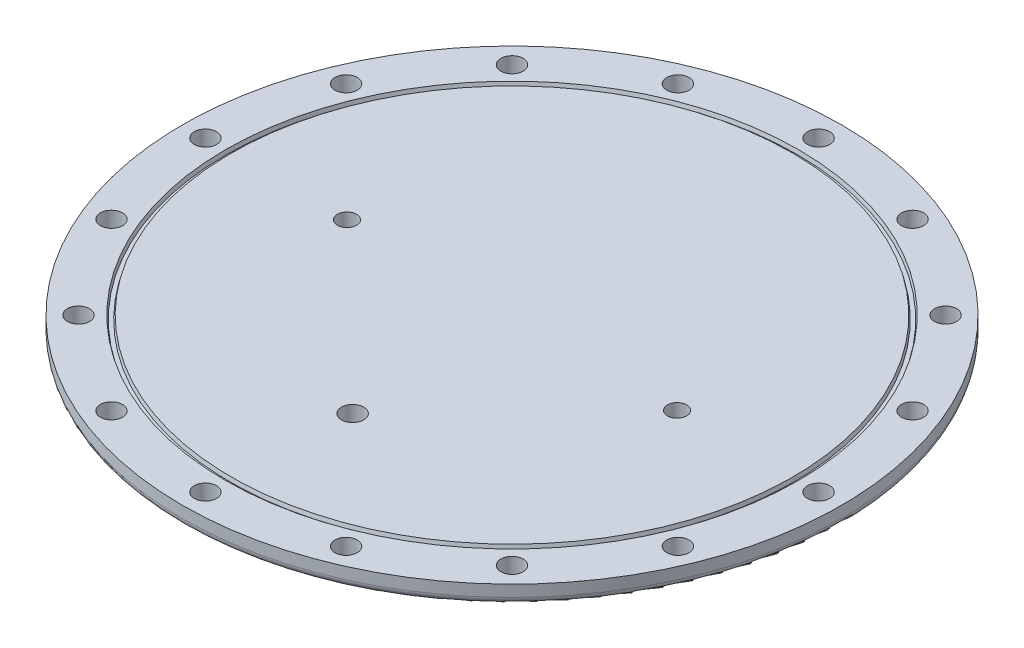
SolidWorks part; units mm, degrees
ref_plane "Front Plane" through (0, 0, 0) normal (0, 0, 1) x (1, 0, 0)
ref_plane "Top Plane" through (0, 0, 0) normal (0, 1, 0) x (1, 0, 0)
ref_plane "Right Plane" through (0, 0, 0) normal (1, 0, 0) x (0, 0, -1)
sketch "Sketch1" plane through (0, 0, 0) normal (0, 1, 0) x (1, 0, 0)
  circle A0 centre (0, 0) radius 86
  dimension "D1" = 172
extrude "Boss-Extrude1" add sketch "Sketch1" along normal blind 5 contours A0
sketch "Sketch2" plane through (0, 5, 0) normal (0, 1, 0) x (1, 0, 0)
  circle A0 centre (0, 0) radius 80 construction
  circle A1 centre (0, 80) radius 2.9
  circle A2 centre (30.6147, 73.9104) radius 2.9
  circle A3 centre (56.5685, 56.5685) radius 2.9
  circle A4 centre (73.9104, 30.6147) radius 2.9
  circle A5 centre (80, 0) radius 2.9
  circle A6 centre (73.9104, -30.6147) radius 2.9
  circle A7 centre (56.5685, -56.5685) radius 2.9
  circle A8 centre (30.6147, -73.9104) radius 2.9
  circle A9 centre (0, -80) radius 2.9
  circle A10 centre (-30.6147, -73.9104) radius 2.9
  circle A11 centre (-56.5685, -56.5685) radius 2.9
  circle A12 centre (-73.9104, -30.6147) radius 2.9
  circle A13 centre (-80, 0) radius 2.9
  circle A14 centre (-73.9104, 30.6147) radius 2.9
  circle A15 centre (-56.5685, 56.5685) radius 2.9
  circle A16 centre (-30.6147, 73.9104) radius 2.9
  point P38 (0, 0)
  dimension "D1" = 160
  dimension "D2" = 5.8
  dimension "D3" = 16
extrude "Cut-Extrude1" cut sketch "Sketch2" against normal up to next
sketch "Sketch5" plane through (0, 0, 0) normal (0, -1, 0) x (1, 0, 0)
  circle A0 centre (43.0643, 0) radius 2.5
  circle A1 centre (-43.0643, 0) radius 2.5
  circle A2 centre (0, 0) radius 43.0643 construction
  circle A3 centre (1.4467, 43.04) radius 2.9
  dimension "D1" = 5
  dimension "D2" = 5.8
extrude "Cut-Extrude2" cut sketch "Sketch5" against normal up to next
sketch "Sketch4" plane through (0, 0, 0) normal (0, 0, 1) x (1, 0, 0)
  line L0 (0, 0) -> (74, 0) construction
  line L1 (-86, 0) -> (86, 0) construction
  line L2 (74, 0) -> (74, 5) construction
  line L3 (76.8104, 5) -> (71.0104, 5) construction
  line L4 (74, 4) -> (74.5, 4)
  line L5 (74.5, 4) -> (74.7679, 5)
  line L6 (74.7679, 5) -> (73.2321, 5)
  line L7 (73.2321, 5) -> (73.5, 4)
  line L8 (73.5, 4) -> (74, 4)
  line L9 (0, 0) -> (0, 12.8224) construction
  dimension "D1" = 74
  dimension "D2" = 1
  dimension "D3" = 1
  dimension "D4" = 75
revolve "Cut-Revolve1" cut sketch "Sketch4" angle 360 about L9
fillet "Fillet1" radius 2 1 edges at (0, 0, 86)
